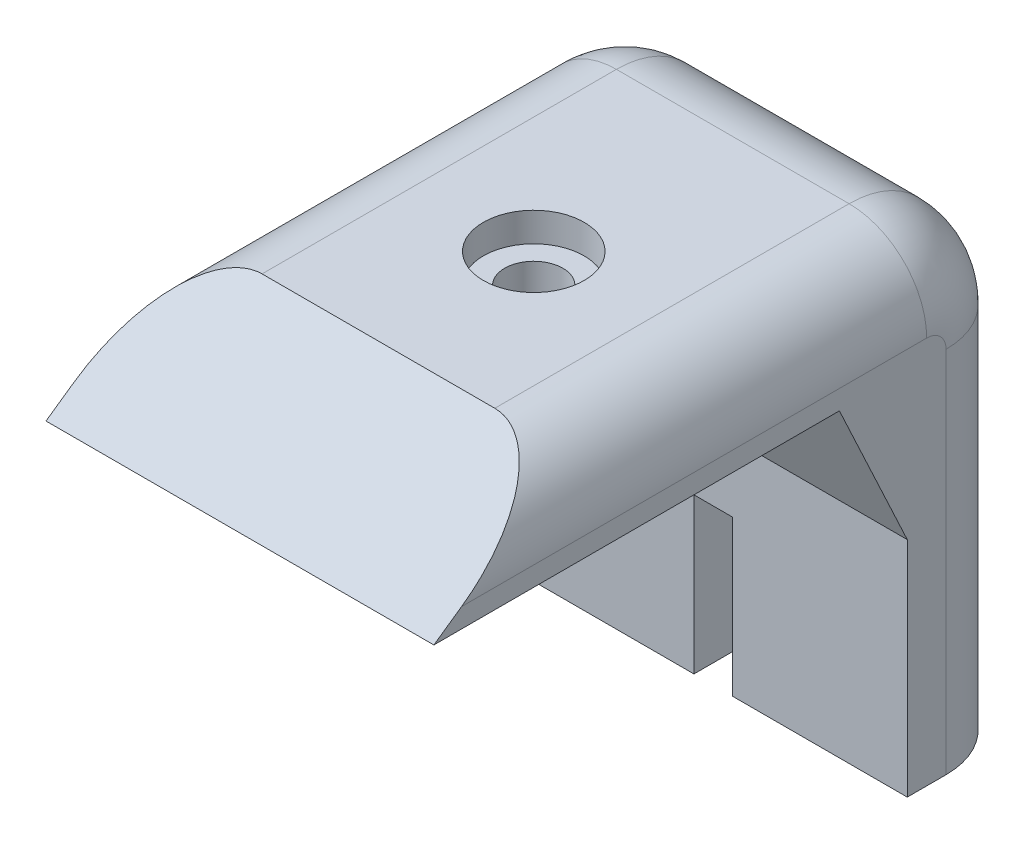
SolidWorks part; units mm, degrees
ref_plane "Front Plane" through (0, 0, 0) normal (0, 0, 1) x (1, 0, 0)
ref_plane "Top Plane" through (0, 0, 0) normal (0, 1, 0) x (1, 0, 0)
ref_plane "Right Plane" through (0, 0, 0) normal (1, 0, 0) x (0, 0, -1)
sketch "Sketch1" plane through (0, 0, 0) normal (1, 0, 0) x (0, 0, -1)
  line L7 (0, 0) -> (7.1407, 5)
  line L8 (24.4101, 0) -> (24.4101, -11)
  line L10 (24.4101, 5) -> (25.4101, 5)
  line L11 (30.4101, 0) -> (30.4101, -11)
  line L12 (24.4101, -11) -> (30.4101, -11)
  line L13 (7.1407, 5) -> (24.4101, 5)
  line L14 (0, 0) -> (24.4101, 0)
  line L16 (24.2851, 0) -> (24.2851, -8) construction
  line L17 (24.2851, -32.5) -> (24.2851, -8) construction
  line L18 (24.2851, -8) -> (24.0351, -8) construction
  line L19 (24.4101, 0) -> (24.4101, 5) construction
  arc A0 (25.4101, 5) -> (30.4101, 0) centre (25.4101, 0) cw
  point P15 (28.4101, 0)
  point P16 (28.4101, -0.2077)
  point P20 (0, 0)
  dimension "D6" = 1
  dimension "D7" = 6
  dimension "D1" = 5
  dimension "D2" = 0.25
  dimension "D3" = 16
  dimension "D4" = 35
extrude "Boss-Extrude1" add sketch "Sketch1" along normal blind 20
sketch "Sketch2" plane through (0, -11, 0) normal (0, -1, 0) x (1, 0, 0)
  line L0 (20, -24.4101) -> (0, -24.4101) construction
  line L1 (20, -30.4101) -> (11, -30.4101)
  line L2 (20, -30.4101) -> (20, -24.4101)
  line L3 (20, -24.4101) -> (11, -24.4101)
  line L4 (11, -30.4101) -> (11, -24.4101)
  line L5 (10, -30.4101) -> (10, -24.4101) construction
  line L6 (20, -30.4101) -> (0, -30.4101) construction
  line L7 (9, -30.4101) -> (9, -24.4101)
  line L8 (0, -24.4101) -> (9, -24.4101)
  line L9 (0, -30.4101) -> (0, -24.4101)
  line L10 (0, -30.4101) -> (9, -30.4101)
  dimension "D1" = 2
extrude "Boss-Extrude2" add sketch "Sketch2" along normal blind 8
chamfer "Chamfer1" distance 3.5 distance2 7.5 1 edges at (10, 0, -24.4101) first distance on face at (10, 0, -12.205)
sketch "Sketch3" plane through (0, 5, 0) normal (0, 1, 0) x (1, 0, 0)
  circle A0 centre (10, 15.1507) radius 1.25 construction
  circle A1 centre (10, 15.1507) radius 1.5
  circle A2 centre (10, 15.1507) radius 2.35 construction
  circle A3 centre (10, 15.1507) radius 2.6
  dimension "D2" = 0.25
  dimension "D1" = 2.5
  dimension "D3" = 4.7
  dimension "D4" = 0.25
extrude "Cut-Extrude1" cut sketch "Sketch3" against normal through all contours A1 region at (10, 5, -15.1507)
extrude "Cut-Extrude2" cut sketch "Sketch3<3>" against normal blind 1.5 contours A3 A1 region at (7.4735, 5, -15.1507)
sketch "Sketch3<3>" plane through (0, 5, 0) normal (0, 1, 0) x (1, 0, 0) same geometry as "Sketch3"
fillet "Fillet1" radius 4 6 edges at (0, 5, -16.2754) (0, 3.5355, -28.9456) (20, 5, -16.2754) (20, 3.5355, -28.9456) (0, -9.5, -30.4101) (20, -9.5, -30.4101)
equation "\"Tolerance\" = 0.25mm"
equation "\"Pocket_Head_M5\"= 8mm"
equation "\"Pocket_Head_M4\" = 7mm"
equation "\"Pocket_Nut_M4\" = 7mm"
equation "\"Pocket_Nut_M2.5\" = 5mm"
equation "\"Pocket_Nut_M5\"= 8mm"
equation "\"Pocket_Nut_M3\"= 5.5mm"
equation "\"Pocket_Head_M3\"= 5.5mm"
equation "\"Pocket_Head_M2.5\" = 4.7mm"
equation "\"Pocket_Head_M6\" = 10mm"
equation "\"D2@Sketch1\"=\"Tolerance\""
equation "\"D2@Sketch3\"=\"Tolerance\""
equation "\"D3@Sketch3\"=\"Pocket_Head_M2.5\""
equation "\"D4@Sketch3\"=\"Tolerance\""
